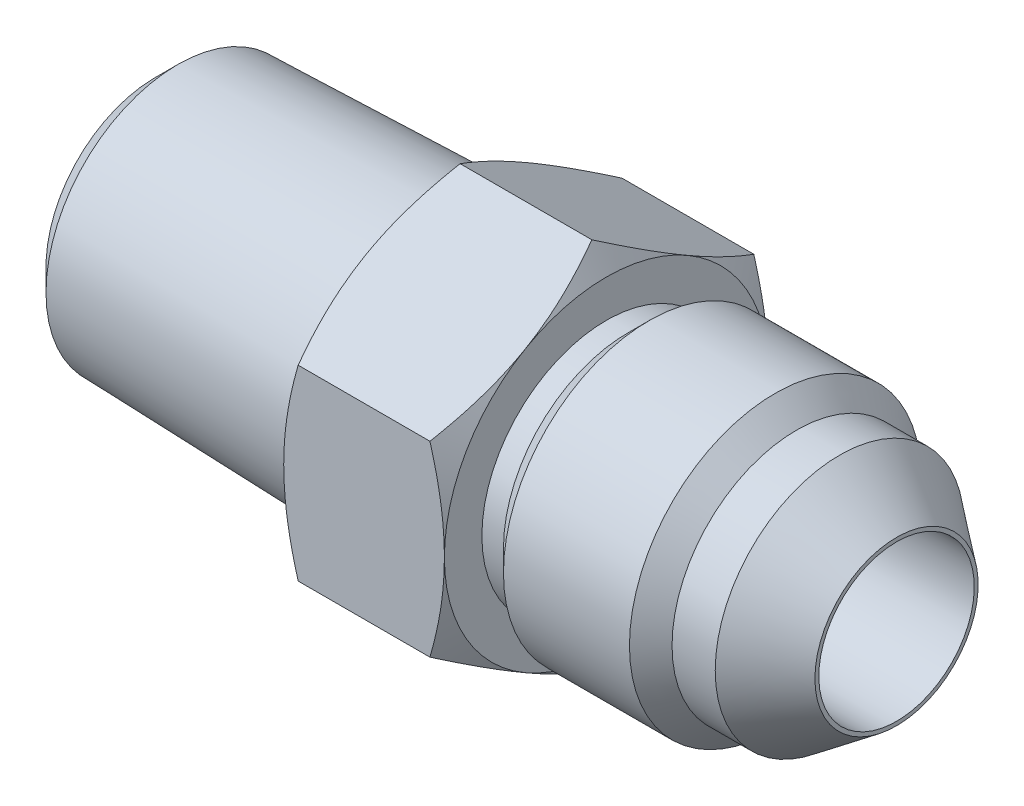
SolidWorks part; units mm, degrees
ref_plane "Front" through (0, 0, 0) normal (0, 0, 1) x (1, 0, 0)
ref_plane "Top" through (0, 0, 0) normal (0, 1, 0) x (1, 0, 0)
ref_plane "Right" through (0, 0, 0) normal (1, 0, 0) x (0, 0, -1)
sketch "Sketch6" plane through (0, 0, 0) normal (0, 0, 1) x (1, 0, 0)
  line L0 (-3.937, 6.858) -> (-3.937, -6.858) construction
  line L1 (18.161, 7.1438) -> (18.161, -7.1438) construction
  line L2 (-18.161, 0) -> (18.161, 0)
  line L4 (-18.161, 0) -> (-18.161, 7.1438)
  line L5 (-18.161, 7.1438) -> (18.161, 7.1438)
  line L6 (18.161, 0) -> (18.161, 7.1438)
  line L7 (-18.161, 3.556) -> (-18.161, -3.556) construction
  line L8 (-3.937, 8.6995) -> (-3.937, -8.6995) construction
  line L9 (3.937, 8.6995) -> (3.937, -8.6995) construction
  point P4 (3.937, 0)
  point P6 (-3.937, 0)
  dimension "Straight Dia" = 14.2875
  dimension "Length" = 36.322
  dimension "L1" = 14.224
  dimension "Pipe OD" = 13.716
  dimension "L2" = 14.224
  dimension "D1" = 7.112
  dimension "D2" = 17.399
revolve "Revolve3" add sketch "Sketch6" angle 360 about L2
sketch "Sketch14" plane through (18.161, 0, 0) normal (-1, 0, 0) x (0, 0, 1)
  circle A1 centre (0, 0) radius 7.1438
  circle A2 centre (0, 0) radius 7.1438
  dimension "D1" = 0
curve "Helix/Spiral1" pitch 1.4111 height 15.6351 turns 11.08 parameters "Pitch"=1.4111
sketch "Sketch15" plane through (0, 0, 0) normal (0, 0, 1) x (1, 0, 0)
  line L0 (18.161, 7.1438) -> (19.3957, 7.1438)
  line L1 (19.3957, 7.1438) -> (18.8666, 6.2272)
  line L2 (18.8666, 6.2272) -> (18.6902, 6.2272)
  line L3 (18.6902, 6.2272) -> (18.161, 7.1438)
  line L4 (18.7784, 6.2272) -> (18.7784, 7.1438) construction
  line L5 (18.4256, 6.6855) -> (19.1311, 6.6855) construction
  dimension "D1" = 60
  dimension "D2" = 0.1764
  dimension "D3" = 0.7056
sweep "Cut-Sweep1" [suppressed] cut profiles "Sketch15" path "Helix/Spiral1"
ref_plane "Plane1" through (-3.937, 0, 0) normal (1, 0, 0) x (0, 0, -1)
sketch "Sketch12" plane through (-3.937, 0, 0) normal (1, 0, 0) x (0, 0, -1)
  line L1 (0, 9.1654) -> (-7.9375, 4.5827)
  line L2 (-7.9375, 4.5827) -> (-7.9375, -4.5827)
  line L3 (-7.9375, -4.5827) -> (0, -9.1654)
  line L4 (0, -9.1654) -> (7.9375, -4.5827)
  line L5 (7.9375, -4.5827) -> (7.9375, 4.5827)
  line L6 (7.9375, 4.5827) -> (0, 9.1654)
  circle A0 centre (0, 0) radius 7.9375 construction
  dimension "Hex" = 15.875
extrude "Extrude1" add sketch "Sketch12" along normal up to vertex (7.874 mm away) up to point (3.937, 0, 0)
sketch "Sketch7" plane through (0, 0, 0) normal (0, 0, 1) x (1, 0, 0)
  line L0 (-18.161, 0) -> (-18.161, 3.81)
  line L2 (-18.161, 3.81) -> (18.161, 3.81)
  line L4 (18.161, 0) -> (18.161, 7.1438) construction
  line L11 (18.161, 3.81) -> (18.161, 0)
  line L12 (18.161, 0) -> (-18.161, 0)
  line L13 (-18.161, 3.81) -> (-18.161, -3.81) construction
  dimension "ID" = 7.62
sketch "Sketch10" plane through (0, 0, 0) normal (0, 0, 1) x (1, 0, 0)
  line L0 (-18.161, 7.1438) -> (18.161, 7.1438) construction
  line L1 (18.161, 7.1438) -> (19.3957, 7.1438) construction
  line L2 (-3.937, -6.858) -> (-18.161, -6.4233) construction
  line L3 (3.937, 9.1654) -> (3.937, 4.5827) construction
  line L5 (0, 0) -> (-18.161, 0) construction
  line L6 (6.0389, 7.1438) -> (3.937, 7.1438)
  line L9 (3.937, 6.1002) -> (3.937, 7.1438)
  line L21 (18.161, 7.1438) -> (12.2144, 7.1438)
  line L22 (12.2144, 7.1438) -> (13.2579, 6.1002)
  line L23 (13.2579, 6.1002) -> (15.3746, 6.1002)
  line L24 (15.3746, 6.1002) -> (18.161, 4.0005)
  line L25 (18.161, 4.0005) -> (18.161, 7.1438)
  line L26 (4.9953, 6.1002) -> (3.937, 6.1002)
  line L27 (6.0389, 7.1438) -> (4.9953, 6.1002)
  point P5 (10.4357, -7.1438)
  point P9 (-11.811, -6.6174)
  dimension "D1" = 8.001
  dimension "D2" = 37
  dimension "D3" = 2.1167
  dimension "D5" = 45
  dimension "D4" = 1.0583
  dimension "D6" = 2.8222
  dimension "D7" = 0.127
  dimension "D9" = 6.35
  dimension "D8" = 1.75
revolve "Cut-Revolve6" cut sketch "Sketch10" angle 360 about L2
revolve "Cut-Revolve5" cut sketch "Sketch7" angle 360 about L12
sketch "Sketch13" plane through (0, 0, 0) normal (0, 0, 1) x (1, 0, 0)
  line L0 (-3.937, 9.1654) -> (-3.937, 7.9375)
  line L1 (-3.937, 4.5827) -> (-3.937, 9.1654) construction
  line L2 (-3.937, 7.9375) -> (-3.2281, 9.1654)
  line L3 (-3.2281, 9.1654) -> (-3.937, 9.1654)
  line L4 (3.2281, 9.1654) -> (3.937, 7.9375)
  line L5 (3.937, 9.1654) -> (3.937, 4.5827) construction
  line L6 (3.937, 7.9375) -> (3.937, 9.1654)
  line L7 (3.937, 9.1654) -> (3.2281, 9.1654)
  dimension "D2" = 30
revolve "Cut-Revolve7" cut sketch "Sketch13" angle 360 about L2
sketch "Sketch17" plane through (-18.161, 0, 0) normal (-1, 0, 0) x (0, 0, 1)
  circle A0 centre (0, 0) radius 7.1438 construction
  circle A1 centre (0, 0) radius 7.1438
extrude "Cut-Extrude1" cut sketch "Sketch17" against normal up to vertex (14.224 mm away) up to point (-3.937, 0, 0)
ref_plane "Plane2" through (-3.937, 0, 0) normal (1, 0, 0) x (0, 0, -1)
sketch "Sketch19" plane through (-3.937, 0, 0) normal (1, 0, 0) x (0, 0, -1)
  circle A0 centre (0, 0) radius 6.858
extrude "Boss-Extrude1" add sketch "Sketch19" against normal up to vertex (14.224 mm away) draft 1.75 separate body up to point (-18.161, 0, 0)
sketch "Sketch20" plane through (-18.161, 0, 0) normal (1, 0, 0) x (0, 0, -1)
  circle A1 centre (0, 0) radius 6.4234
  circle A2 centre (0, 0) radius 6.4234 construction
sketch "Sketch21" plane through (0, 0, 0) normal (0, 0, 1) x (1, 0, 0)
  line L0 (-19.3641, 6.3033) -> (-18.2303, 6.3033) construction
  line L1 (-19.5028, 6.5435) -> (-18.7972, 5.3215) construction
  line L2 (-18.9173, 5.5295) -> (-18.6771, 5.5295)
  line L3 (-18.7972, 5.3215) -> (-18.0917, 6.5435) construction
  line L4 (-18.7972, 5.3215) -> (-18.6771, 5.5295) construction
  line L5 (-18.7972, 6.3033) -> (-18.7972, 6.5435) construction
  line L6 (-19.5028, 6.5435) -> (-18.0917, 6.5435) construction
  line L7 (-18.7972, 6.4234) -> (-18.161, 6.4234) construction
  line L8 (-18.0917, 6.5435) -> (-19.4334, 6.4234)
  line L9 (-19.4334, 6.4234) -> (-18.9173, 5.5295)
  line L10 (-18.6771, 5.5295) -> (-18.0917, 6.5435)
  line L11 (-18.7972, 5.3215) -> (-18.7972, 5.5295) construction
  dimension "D2" = 0.2402
  dimension "D1" = 1.4111
curve "Helix/Spiral2" parameters "Pitch"=1.4111
chamfer "Chamfer1" distance 1.0583 angle 45 1 edges at (-18.161, 0, -6.4234) first distance on face at (-18.161, 0, -6.4234)
sketch "Sketch22" plane through (-3.937, 0, 0) normal (1, 0, 0) x (0, 0, -1)
  circle A1 centre (0, 0) radius 6.858
  circle A2 centre (0, 0) radius 6.858
  dimension "D1" = 0
sweep "Cut-Sweep2" [suppressed] cut profiles "Sketch21" path "Helix/Spiral2"
extrude "Boss-Extrude3" add sketch "Sketch22" against normal up to vertex (14.224 mm away) draft 15 up to point (-18.161, 7.1438, 0)
combine bodies "Combine1" operation type add bodies to combine 173 169
sketch "Sketch23" plane through (-18.161, 0, 0) normal (-1, 0, 0) x (0, 0, 1)
  circle A2 centre (0, 0) radius 3.556
extrude "Cut-Extrude2" cut sketch "Sketch23" against normal up to vertex (14.224 mm away) up to point (-3.937, 0, 0)
other "CPoint1" parameters "Diameter"=9.525, "StubLength"=38.1
ref_axis "Axis1" through (28.161, 0, 0) along (-1, 0, 0)
equation "\"D3@Helix/Spiral1\" = \"L1@Sketch6\"+\"Pitch@Helix/Spiral1\""
equation "\"D2@Sketch15\" = \"Pitch@Helix/Spiral1\"*.125"
equation "\"D3@Sketch15\" = \"Pitch@Helix/Spiral1\"*.5"
equation "\"D3@Sketch10\" = \"Pitch@Helix/Spiral1\"*1.5"
equation "\"D1@Sketch10\" = \"ID@Sketch7\"*1.05"
equation "\"D1@Sketch21\" = \"Pitch@Helix/Spiral2\""
equation "\"D3@Helix/Spiral2\" = \"L2@Sketch6\"+\"Pitch@Helix/Spiral2\""
equation "\"D1@Chamfer1\" = \"Pitch@Helix/Spiral2\"*.75"
equation "\"D4@Sketch10\" = \"Pitch@Helix/Spiral1\"*.75"
equation "\"D6@Sketch10\" = \"Pitch@Helix/Spiral1\"*2"
equation "\"D9@Sketch10\" = \"Pitch@Helix/Spiral2\"*4.5"
equation "\"D2@Sketch6\" = \"Hex@Sketch12\"+.06"
